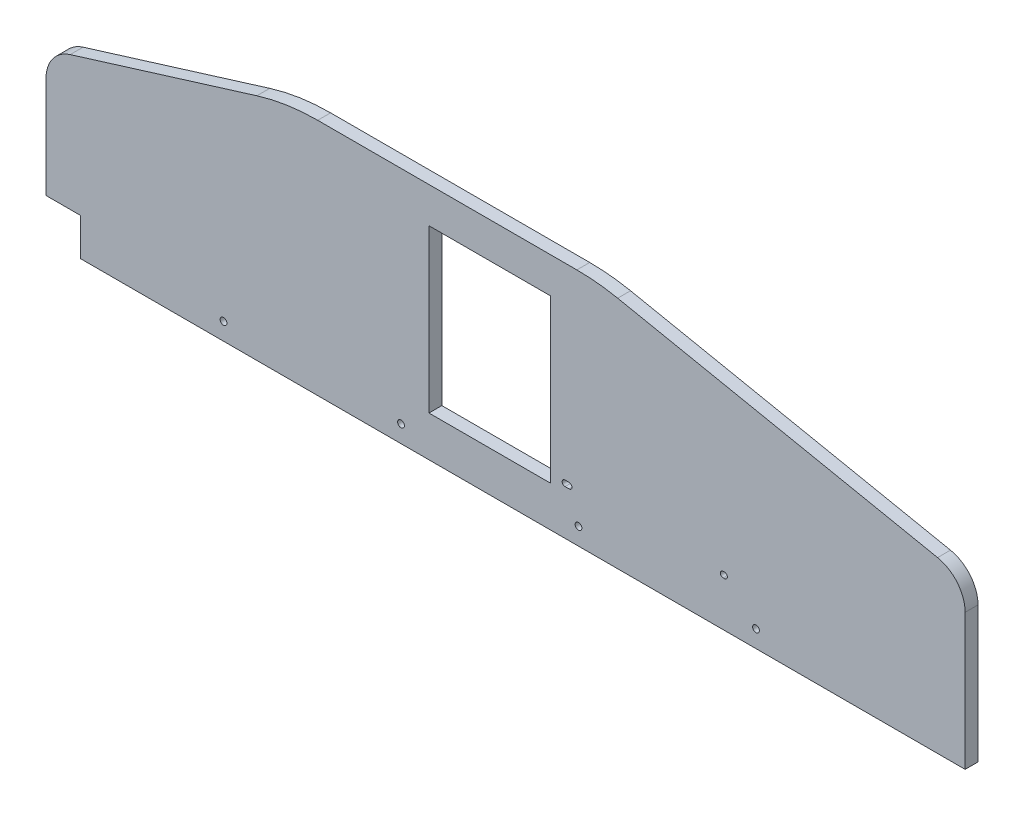
SolidWorks part; units mm, degrees
material "PC High Viscosity"
ref_plane "Front Plane" through (0, 0, 0) normal (0, 0, 1) x (1, 0, 0)
ref_plane "Top Plane" through (0, 0, 0) normal (0, 1, 0) x (1, 0, 0)
ref_plane "Right Plane" through (0, 0, 0) normal (1, 0, 0) x (0, 0, -1)
sketch "Sketch2" plane through (0, 0, 0) normal (0, 0, 1) x (1, 0, 0)
  line L0 (-340, 26.4) -> (-340, 121.4)
  line L1 (68, 176.4) -> (-162, 176.4)
  line L2 (68, 176.4) -> (340, 121.4)
  line L3 (340, 121.4) -> (340, 26.4)
  line L4 (340, 26.4) -> (340, 0)
  line L5 (-162, 176.4) -> (-340, 121.4)
  line L6 (340, 0) -> (-340, 0)
  line L7 (-340, 0) -> (-340, 26.4)
  dimension "D1" = 150
  dimension "D2" = 680
  dimension "D3" = 95
  dimension "D4" = 408
  dimension "D5" = 178
  dimension "D8" = 95
  dimension "D9" = 26.4
extrude "Boss-Extrude1" add sketch "Sketch2" along normal mid plane 9.525
fillet "Fillet1" radius 25.4 2 edges at (340, 121.4, 0) (-340, 121.4, 0)
sketch "Sketch3" plane through (0, 0, 4.7625) normal (0, 0, 1) x (1, 0, 0)
  line L0 (0, 0) -> (0, 192.0016) construction
  line L1 (-340, 0) -> (-314.6, 0)
  line L2 (-340, 0) -> (-340, 27.686)
  line L3 (-340, 27.686) -> (-314.6, 27.686)
  line L4 (-314.6, 0) -> (-314.6, 27.686)
  line L5 (0, 192.0016) -> (0, -60.0751) construction
  dimension "D1" = 25.4
  dimension "D2" = 27.686
extrude "Cut-Extrude1" cut sketch "Sketch3" against normal through all
sketch "Sketch5" plane through (0, 0, 4.7625) normal (0, 0, 1) x (1, 0, 0)
  line L0 (-340, 102.6634) -> (-340, 27.686) construction
  line L1 (-56.6685, 150) -> (33.3315, 150)
  line L2 (-56.6685, 150) -> (-56.6685, 30)
  line L3 (-56.6685, 30) -> (33.3315, 30)
  line L4 (33.3315, 150) -> (33.3315, 30)
  line L5 (-56.6685, 150) -> (33.3315, 30) construction
  line L6 (-56.6685, 30) -> (33.3315, 150) construction
  line L8 (-314.6, 0) -> (340, 0) construction
  point P5 (-11.6685, 90)
  dimension "D1" = 120
  dimension "D2" = 90
  dimension "D3" = 30
  dimension "D4" = 328.3315
extrude "Cut-Extrude2" cut sketch "Sketch5" against normal through all
hole_wizard "Tap Drill for M6x1.0 Tap1" positions "Sketch7" profile "Sketch6" hole size "M6x1.0" standard "ANSI Metric" end condition through all
sketch "Sketch7" plane through (0, 0, 4.7625) normal (0, 0, 1) x (1, 0, 0)
  line L0 (-314.6, 0) -> (340, 0) construction
  line L1 (-340, 102.6634) -> (-340, 27.686) construction
  point P0 (-208.682, 12.7)
  point P2 (-77.364, 12.7)
  point P4 (53.954, 12.7)
  point P6 (185.272, 12.7)
  dimension "D1" = 12.7
  dimension "D2" = 131.318
  dimension "D3" = 131.318
  dimension "D4" = 131.318
  dimension "D5" = 131.318
sketch "Sketch6" plane through (-208.682, 12.7, 4.7625) normal (1, 0, 0) x (0, -1, 0)
  line L0 (0, 0) -> (0, 9.525)
  line L1 (0, 9.525) -> (2.5, 9.525)
  line L2 (2.5, 9.525) -> (2.5, 0)
  line L5 (2.5, 0) -> (0, 0)
  line L11 (0, -6.35) -> (0, 107.95) construction
  dimension "Thru Hole Dia." = 5
  dimension "Thru Hole Depth" = 9.525
sketch "Sketch8" plane through (0, 0, 4.7625) normal (0, 0, 1) x (1, 0, 0)
  line L0 (161, 35.3) -> (162, 35.3) construction
  line L1 (161, 37.4) -> (162, 37.4)
  line L2 (161, 33.2) -> (162, 33.2)
  line L3 (47, 35.3) -> (44, 35.3) construction
  line L4 (47, 33.2) -> (44, 33.2)
  line L5 (47, 37.4) -> (44, 37.4)
  line L6 (-314.6, 0) -> (340, 0) construction
  line L10 (-340, 102.6634) -> (-340, 27.686) construction
  arc A0 (161, 37.4) -> (161, 33.2) centre (161, 35.3) ccw
  arc A1 (162, 33.2) -> (162, 37.4) centre (162, 35.3) ccw
  arc A2 (47, 33.2) -> (47, 37.4) centre (47, 35.3) ccw
  arc A3 (44, 37.4) -> (44, 33.2) centre (44, 35.3) ccw
  point P2 (161.5, 35.3)
  point P9 (45.5, 35.3)
  dimension "D2" = 1
  dimension "D1" = 2.1
  dimension "D3" = 35.3
  dimension "D4" = 384
  dimension "D5" = 115.5
  dimension "D6" = 3
extrude "Cut-Extrude3" cut sketch "Sketch8" against normal through all
fillet "Fillet2" radius 152.4 2 edges at (68, 176.4, 0) (-162, 176.4, 0)
